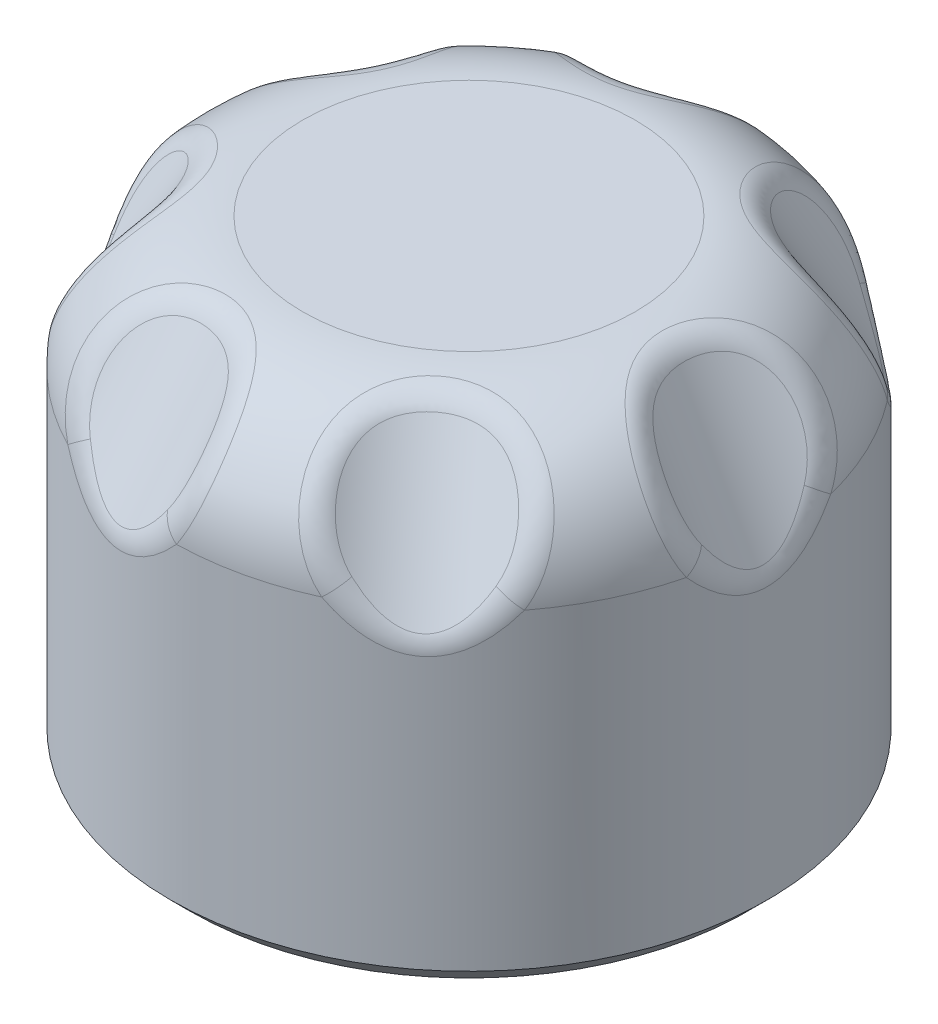
SolidWorks part; units mm, degrees
ref_plane "Front Plane" through (0, 0, 0) normal (0, 0, 1) x (1, 0, 0)
ref_plane "Top Plane" through (0, 0, 0) normal (0, 1, 0) x (1, 0, 0)
ref_plane "Right Plane" through (0, 0, 0) normal (1, 0, 0) x (0, 0, -1)
sketch "Sketch2" plane through (0, 0, 0) normal (0, 1, 0) x (1, 0, 0)
  circle A0 centre (0, 0) radius 10.025 construction
  circle A1 centre (0, 0) radius 9.025
  dimension "D1" = 20.05
  dimension "D2" = 1
extrude "Boss-Extrude1" add sketch "Sketch2" along normal blind 14
fillet "Fillet1" radius 4 1 edges at (0, 14, 9.025)
sketch "Sketch3" plane through (0, 0, 0) normal (0, 0, 1) x (1, 0, 0)
  line L0 (0, 32.7036) -> (17.7267, 2) construction
  line L2 (0, 32.7036) -> (0, 0) construction
  line L3 (0, 32.7036) -> (17.7267, 2)
  line L4 (0, 32.7036) -> (-3.4641, 30.7036)
  line L5 (17.7267, 2) -> (14.2626, 0)
  line L6 (-3.4641, 30.7036) -> (14.2626, 0)
  line L7 (0, 26.7036) -> (8.1558, 12.5774) construction
  arc A0 (9.025, 10) -> (5.025, 14) centre (5.025, 10) ccw construction
  dimension "D1" = 1
  dimension "D2" = 30
  dimension "D3" = 4
revolve "Cut-Revolve1" cut sketch "Sketch3" angle 360 about L3
sketch3d "3DSketch1"
  line L0 (0, 14, 0) -> (0, 0, 0)
  line L1 (0, 4.8324, 0) -> (0, 20.3352, 0) construction
fillet "Fillet2" radius 1 2 edges at (9.025, 9.0718, 0.0031) (6.3016, 13.7906, -0.0841)
pattern_circular "CirPattern1" count 7 over 360 of "Cut-Revolve1", "Fillet2" reverse direction yes
sketch "Sketch5" plane through (0, 0, 0) normal (0, 0, 1) x (1, 0, 0)
  line L0 (0, 12) -> (0, 0) construction
  line L1 (5.025, 14) -> (-5.025, 14) construction
  line L2 (0, 12) -> (3.15, 12)
  line L3 (3.15, 12) -> (3.15, 1)
  line L4 (3.15, 1) -> (3.75, 1)
  line L5 (3.75, 1) -> (3.75, 0)
  line L6 (3.75, 0) -> (0, 0)
  line L7 (0, 12) -> (0, 0)
  line L8 (-9.025, 0) -> (9.025, 0) construction
  dimension "D1" = 2
  dimension "D2" = 3.15
  dimension "D3" = 3.75
  dimension "D4" = 11
revolve "Cut-Revolve2" cut sketch "Sketch5" angle 360 about L0
sketch "Sketch7" plane through (0, 12, 0) normal (0, -1, 0) x (1, 0, 0)
  line L0 (-1.6, 2.7134) -> (-1.6, -2.7134)
  circle A0 centre (0, 0) radius 3.15 construction
  circle A1 centre (0, 0) radius 3.15 construction
  arc A2 (-1.6, 2.7134) -> (-1.6, -2.7134) centre (0, 0) ccw
  point P9 (3.15, 0)
  dimension "D1" = 4.75
extrude "Boss-Extrude2" add sketch "Sketch7" along normal blind 6.75
chamfer "Chamfer1" distance 1.5 angle 45 1 edges at (-1.6, 5.25, 0)
chamfer "Chamfer2" distance 0.75 angle 45 1 edges at (-3.15, 1, 0)
chamfer "Chamfer3" distance 0.6 angle 45 1 edges at (0, 0, 9.025)
